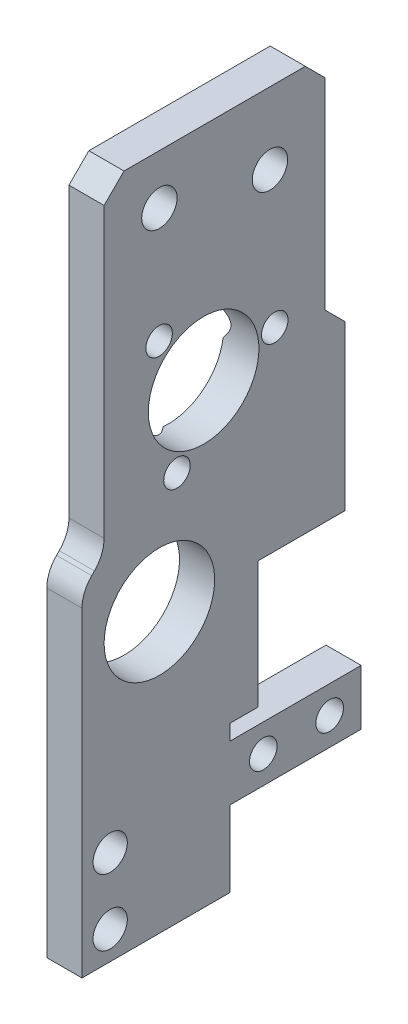
SolidWorks part; units mm, degrees
ref_plane "Front Plane" through (0, 0, 0) normal (0, 0, 1) x (1, 0, 0)
ref_plane "Top Plane" through (0, 0, 0) normal (0, 1, 0) x (1, 0, 0)
ref_plane "Right Plane" through (0, 0, 0) normal (1, 0, 0) x (0, 0, -1)
sketch "Sketch1" plane through (0, 0, 0) normal (1, 0, 0) x (0, 0, -1)
  line L2 (0, 0) -> (0, 30.2)
  line L3 (0, 30.2) -> (2, 32.2)
  line L4 (2, 32.2) -> (2, 61.31)
  line L5 (2, 61.31) -> (22, 61.31)
  line L7 (23.8, 24.71) -> (15.9, 24.71)
  line L8 (13.4, 13.26) -> (13.4, 11.86)
  line L9 (13.4, 11.86) -> (25.25, 11.86)
  line L10 (25.25, 11.86) -> (25.25, 6.86)
  line L11 (25.25, 6.86) -> (13.4, 6.86)
  line L12 (13.4, 6.86) -> (13.4, 0)
  line L13 (13.4, 0) -> (0, 0)
  line L14 (-6.9356, -4) -> (62.4069, -4) construction
  line L15 (7, 30.2) -> (0, 30.2) construction
  line L16 (7, 20.2) -> (0, 20.2) construction
  line L17 (2, 18.2) -> (2, 32.2) construction
  line L18 (13.4, 13.26) -> (15.9, 13.26)
  line L19 (15.9, 13.26) -> (15.9, 24.71)
  line L23 (22, 61.31) -> (22, 41.31)
  line L24 (22, 41.31) -> (23.8, 41.31)
  line L25 (23.8, 41.31) -> (23.8, 24.71)
  circle A0 centre (7, 25.2) radius 5
  circle A1 centre (7, 56.81) radius 1.6
  circle A2 centre (17, 54.81) radius 1.6
  circle A3 centre (22.4, 9.36) radius 1.25
  circle A4 centre (16.4, 9.36) radius 1.25
  circle A5 centre (2.55, 2.55) radius 1.55
  circle A6 centre (2.55, 8.55) radius 1.55
  circle A7 centre (22.4, 9.36) radius 2.85 construction
  circle A8 centre (16.4, 9.36) radius 2.85 construction
  point P39 (0, 0)
  point P40 (0, 0)
  dimension "D11" = 10
  dimension "D13" = 3.2
  dimension "D17" = 5
  dimension "D21" = 2.5
  dimension "D29" = 7.9
  dimension "D33" = 3.1
  dimension "D34" = 5.7
  dimension "D3" = 10.86
  dimension "D4" = 5
  dimension "D5" = 12.85
  dimension "D6" = 11.85
  dimension "D7" = 61.31
  dimension "D8" = 4
  dimension "D9" = 2
  dimension "D10" = 2
  dimension "D12" = 29.2
  dimension "D14" = 6.5
  dimension "D15" = 4.5
  dimension "D16" = 5
  dimension "D18" = 6
  dimension "D19" = 1.45
  dimension "D20" = 2.5
  dimension "D22" = 1.4
  dimension "D24" = 20
  dimension "D26" = 1.8
  dimension "D27" = 20
  dimension "D28" = 2
  dimension "D30" = 6
  dimension "D31" = 2.55
  dimension "D32" = 2.55
extrude "Boss-Extrude1" add sketch "Sketch1" along normal blind 3.18
chamfer "Chamfer1" [suppressed] distance 2.5 angle 63.43
fillet "Fillet1" [suppressed] radius 1
sketch "Sketch3" plane through (0, 0, 0) normal (-1, 0, 0) x (0, 0, 1)
  line L1 (-17.4326, 42.2448) -> (-6.9749, 46.4147) construction
  line L2 (-6.9749, 46.4147) -> (-8.5925, 35.2732) construction
  line L3 (-8.5925, 35.2732) -> (-17.4326, 42.2448) construction
  line L4 (-2, 61.31) -> (-2, 32.2) construction
  circle A0 centre (-11, 41.3109) radius 5
  circle A2 centre (-11, 41.3109) radius 6.5 construction
  circle A3 centre (-6.9749, 46.4147) radius 1.2 construction
  circle A4 centre (-8.5925, 35.2732) radius 1.2 construction
  circle A5 centre (-17.4326, 42.2448) radius 1.2 construction
  circle A6 centre (-7, 25.2) radius 5 construction
  dimension "D1" = 10
  dimension "D3" = 16.6
  dimension "D4" = 13
  dimension "D5" = 2.4
  dimension "D2" = 9
hole_wizard "CSK for M2 Flat Head Machine Screw1" positions "Sketch6" profile "Sketch7" countersink size "M2" standard "ANSI Metric"
sketch "Sketch6" plane through (0, 0, 0) normal (-1, 0, 0) x (0, 0, 1)
  point P0 (-6.9749, 46.4147)
  point P3 (-17.4326, 42.2448)
  point P6 (-8.5925, 35.2732)
sketch "Sketch7" plane through (0, 46.4147, -6.9749) normal (0, 1, 0) x (0, 0, 1)
  line L0 (0, 0) -> (0, 4.23)
  line L1 (0, 4.23) -> (1.2, 3.509)
  line L2 (1.2, 3.509) -> (1.2, 1)
  line L3 (1.2, 1) -> (2.2, 0)
  line L5 (2.2, 0) -> (0, 0)
  line L6 (-1.2, 1) -> (-2.2, 0) construction
  line L10 (0, 4.23) -> (-1.2, 3.509) construction
  line L11 (0, -6.35) -> (0, 107.95) construction
  dimension "Hole Dia." = 2.4
  dimension "Hole Depth" = 4.23
  dimension "Near C'Sink Dia." = 4.4
  dimension "Near C'Sink Angle" = 90
  dimension "Drill Angle" = 118
extrude "Cut-Extrude4" cut sketch "Sketch3" against normal through all
sketch "Sketch8" [suppressed] plane through (3.18, 0, 0) normal (1, 0, 0) x (0, 0, -1)
  line L0 (2, 61.31) -> (2, 32.2) construction
  line L1 (11, 41.3109) -> (2, 41.3109) construction
  line L2 (2, 44.3109) -> (4.1261, 44.3109)
  line L3 (4.1261, 38.3109) -> (2, 38.3109)
  line L4 (2, 38.3109) -> (2, 44.3109)
  arc A0 (4.1261, 38.3109) -> (4.1261, 44.3109) centre (11, 41.3109) ccw
  circle A1 centre (7, 25.2) radius 5 construction
  point P11 (2, 41.3109)
  dimension "D1" = 16.6
  dimension "D2" = 15
  dimension "D3" = 9
  dimension "D4" = 6
extrude "Cut-Extrude5" [suppressed] cut sketch "Sketch8" against normal through all
fillet "Fillet2" radius 3 2 edges at (1.59, 30.2, 0) (1.59, 32.2, -2)
fillet "Chamfer2" radius 1.8 3 edges at (1.59, 61.31, -22) (1.59, 61.31, -2) (1.59, 41.31, -23.8) profile chamfer
fillet "Fillet4" [suppressed] radius 0.5
equation "\"7.5.00mm\"=5"
